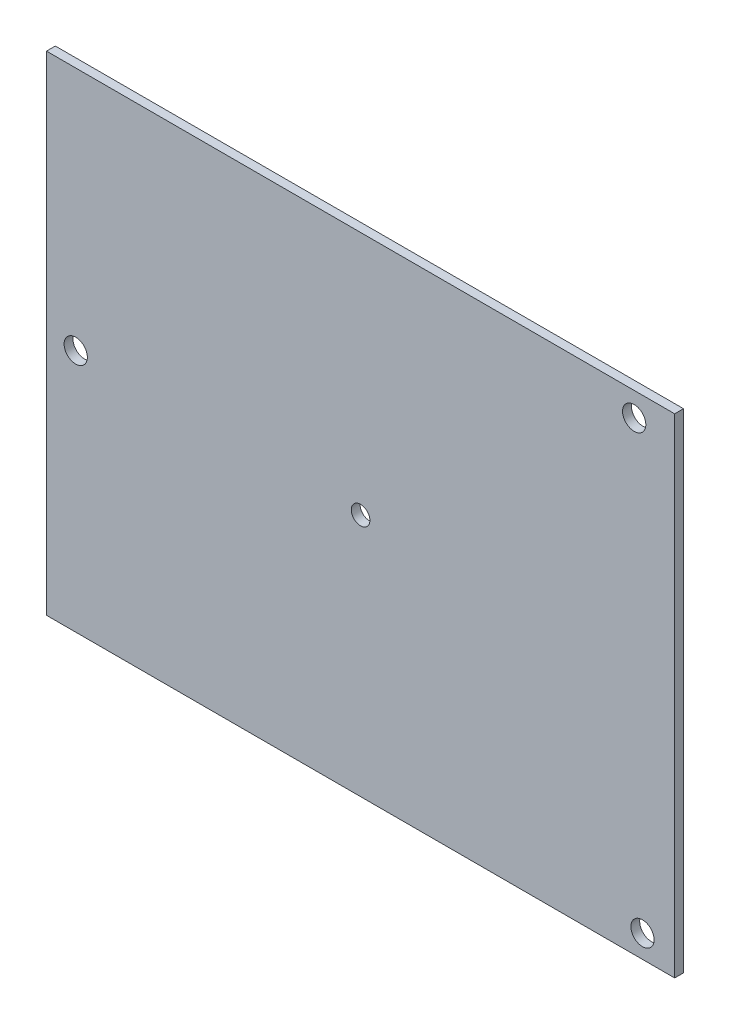
SolidWorks part; units mm, degrees
ref_plane "Front Plane" through (0, 0, 0) normal (0, 0, 1) x (1, 0, 0)
ref_plane "Top Plane" through (0, 0, 0) normal (0, 1, 0) x (1, 0, 0)
ref_plane "Right Plane" through (0, 0, 0) normal (1, 0, 0) x (0, 0, -1)
sketch "Sketch1" plane through (0, 0, 0) normal (0, 0, 1) x (1, 0, 0)
  line L1 (-25.8848, 108.0423) -> (109.1152, 108.0423)
  line L2 (-25.8848, 108.0423) -> (-25.8848, 3.0423)
  line L3 (-25.8848, 3.0423) -> (109.1152, 3.0423)
  line L4 (109.1152, 108.0423) -> (109.1152, 3.0423)
  dimension "D1" = 135
  dimension "D2" = 105
base flange "Base-Flange1" sketch "Sketch1" thickness 1.8974 reverse thickness direction no parameters "D1"=2.54
sketch "Sketch6" plane through (0, 0, 0) normal (0, 0, 1) x (1, 0, 0)
  line L0 (109.1152, 108.0423) -> (-25.8848, 108.0423) construction
  line L1 (109.1152, 3.0423) -> (109.1152, 108.0423) construction
  circle A0 centre (-19.5986, 55.4388) radius 2.5
  circle A1 centre (100.4106, 102.9156) radius 2.5
  circle A2 centre (102.1939, 7.9153) radius 2.5
  circle A3 centre (41.6152, 55.4388) radius 2
  point P9 (41.6152, 108.0423)
  point P10 (109.1152, 55.5423)
  dimension "D1" = 5
extrude "Cut-Extrude1" cut sketch "Sketch6" against normal blind 2 normal cut yes
sketch "Bend-Lines1" plane through (0, 0, 0) normal (0, 1, 0) x (1, 0, 0)
sketch "Bounding-Box1" plane through (0, 0, 0) normal (0, 1, 0) x (1, 0, 0)
sheet metal parameters "Sheet-Metal1" thickness 1.8974 parameters "D1"=2.54
flat pattern "Flat-Pattern1" [suppressed]
sketch "Bend-Lines2" plane through (0, 0, 0) normal (0, 1, 0) x (1, 0, 0)
sketch "Bounding-Box2" [suppressed] plane through (0, 0, 0) normal (0, 1, 0) x (1, 0, 0)
sheet metal parameters "Sheet-Metal2" thickness 1.8974 parameters "D1"=2.54
flat pattern "Flat-Pattern1"
sketch "Bend-Lines2" plane through (0, 0, 0) normal (0, 1, 0) x (1, 0, 0)
sketch "Bounding-Box2" [suppressed] plane through (0, 0, 0) normal (0, 1, 0) x (1, 0, 0)
